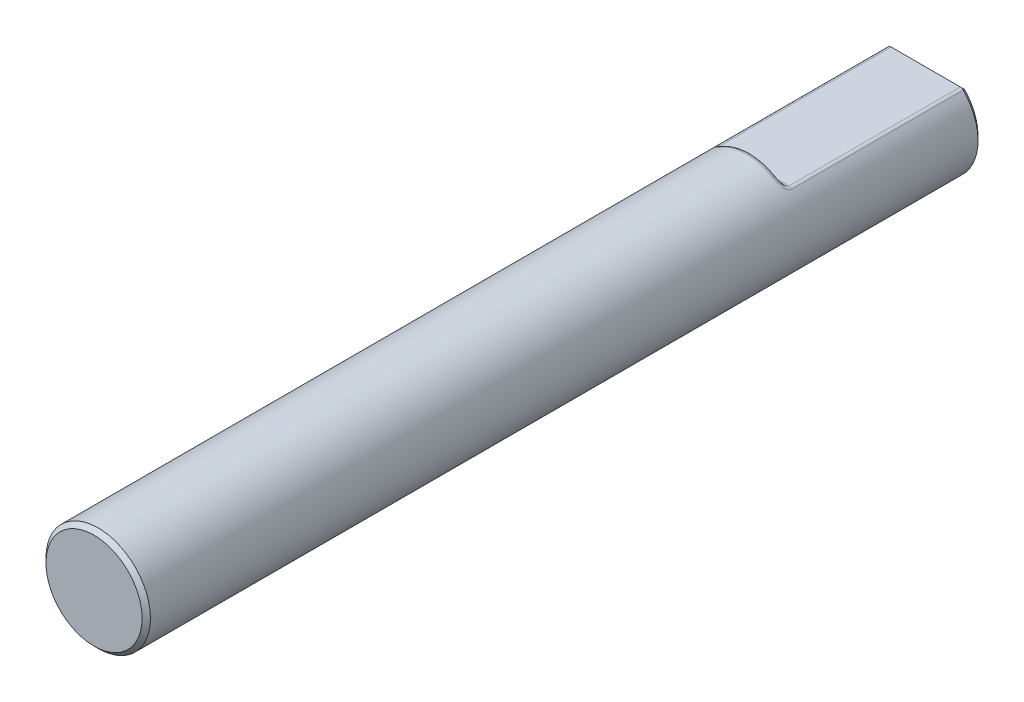
SolidWorks part; units mm, degrees
ref_plane "Front Plane" through (0, 0, 0) normal (0, 0, 1) x (1, 0, 0)
ref_plane "Top Plane" through (0, 0, 0) normal (0, 1, 0) x (1, 0, 0)
ref_plane "Right Plane" through (0, 0, 0) normal (1, 0, 0) x (0, 0, -1)
sketch "Sketch1" plane through (0, 0, 0) normal (0, 0, 1) x (1, 0, 0)
  circle A0 centre (0, 0) radius 3.175
  dimension "D1" = 6.35
extrude "Boss-Extrude1" add sketch "Sketch1" along normal blind 50.8
sketch "Sketch2" plane through (0, 0, 0) normal (0, 0, -1) x (-1, 0, 0)
  line L0 (-2.2034, 2.286) -> (2.2034, 2.286)
  line L1 (0, 0) -> (3.175, 0)
  circle A0 centre (0, 0) radius 3.175 construction
  arc A1 (-2.2034, 2.286) -> (2.2034, 2.286) centre (0, 0) cw
  point P5 (0, 3.175)
  circle M3 centre (0, 0) radius 3.175
  dimension "D1" = 0.889
extrude "Cut-Extrude1" cut sketch "Sketch2" against normal blind 10.922 contours L0 M3 region at (0, 2.6462, 0)
chamfer "Chamfer1" distance 0.254 angle 45 3 edges at (0, 2.286, 0) (0, -3.175, 0) (3.175, 0, 50.8)
fillet "Fillet1" radius 0.254 4 edges at (2.2034, 2.286, 5.588) (-2.2034, 2.286, 5.588) (0, 3.175, 10.922) (0, 2.286, 10.922)
